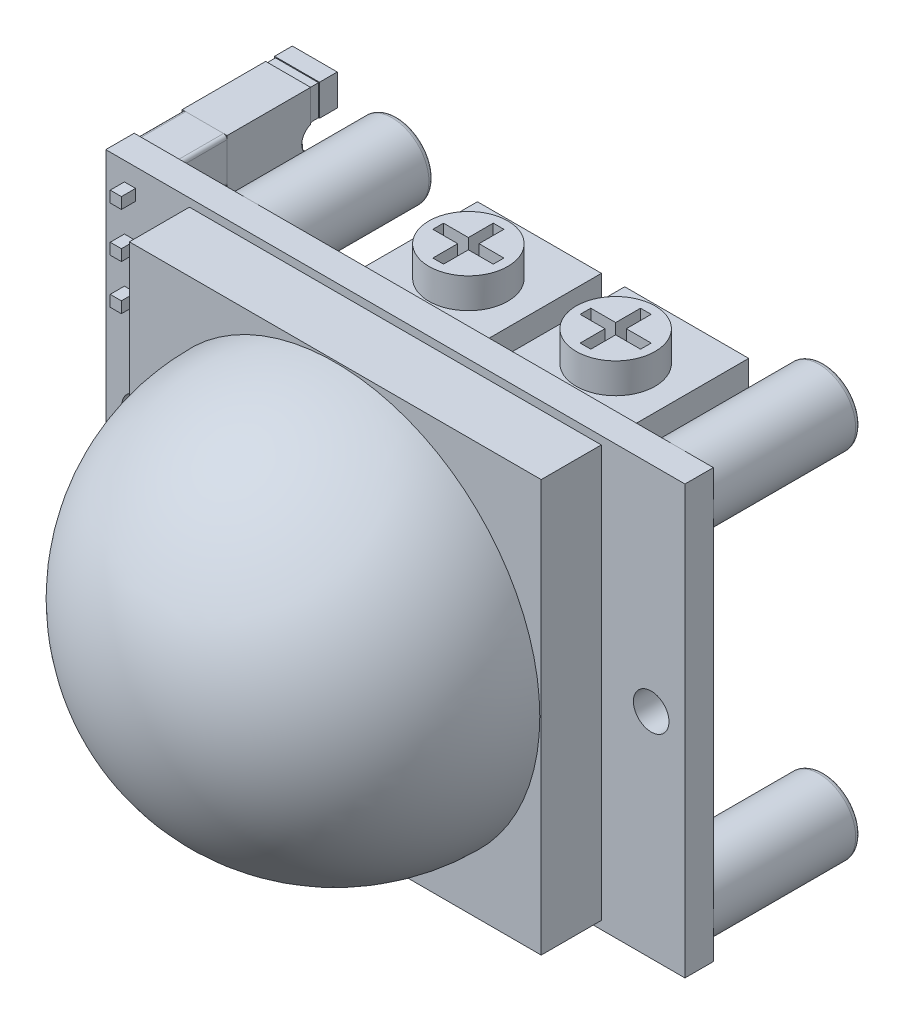
SolidWorks part; units mm, degrees
material "S235 (E24)"
ref_plane "Plan1" through (0, 0, 0) normal (0, 0, 1) x (1, 0, 0)
ref_plane "Plan2" through (0, 0, 0) normal (0, 1, 0) x (1, 0, 0)
ref_plane "Plan3" through (0, 0, 0) normal (1, 0, 0) x (0, 0, -1)
sketch "Esquisse1" plane through (0, 0, 0) normal (0, 0, 1) x (1, 0, 0)
  line L1 (-16.3, 12.04) -> (16.3, 12.04)
  line L2 (-16.3, 12.04) -> (-16.3, -12.04)
  line L3 (-16.3, -12.04) -> (16.3, -12.04)
  line L4 (16.3, 12.04) -> (16.3, -12.04)
  line L5 (-16.3, 12.04) -> (16.3, -12.04) construction
  line L6 (-16.3, -12.04) -> (16.3, 12.04) construction
  point P0 (0, 0)
  dimension "D1" = 24.08
  dimension "D2" = 32.6
extrude "Boss.-Extru.1" add sketch "Esquisse1" along normal blind 1.6
sketch "Esquisse2" plane through (0, 0, 1.6) normal (0, 0, 1) x (1, 0, 0)
  line L1 (-11.59, 11.59) -> (11.59, 11.59)
  line L2 (-11.59, 11.59) -> (-11.59, -11.59)
  line L3 (-11.59, -11.59) -> (11.59, -11.59)
  line L4 (11.59, 11.59) -> (11.59, -11.59)
  line L5 (-11.59, 11.59) -> (11.59, -11.59) construction
  line L6 (-11.59, -11.59) -> (11.59, 11.59) construction
  point P0 (0, 0)
  dimension "D1" = 23.18
extrude "Boss.-Extru.2" add sketch "Esquisse2" along normal blind 3.38
sketch "Esquisse3" plane through (0, 0, 0) normal (0, 1, 0) x (1, 0, 0)
  line L0 (11.59, -4.98) -> (-11.59, -4.98) construction
  line L1 (11.51, -4.98) -> (0, -4.98)
  line L2 (0, -4.98) -> (0, -16.49)
  arc A0 (0, -16.49) -> (11.51, -4.98) centre (0, -4.98) ccw
  dimension "D1" = 23.02
revolve "Révolution1" add sketch "Esquisse3" angle 360 about L2
sketch "Esquisse4" plane through (0, 0, 0) normal (0, 0, -1) x (-1, 0, 0)
  line L0 (16.3, -12.04) -> (-16.3, -12.04) construction
  line L1 (16.3, 12.04) -> (16.3, -12.04) construction
  line L2 (-16.3, -12.04) -> (-16.3, 12.04) construction
  line L3 (-16.3, 12.04) -> (16.3, 12.04) construction
  circle A0 centre (-14.24, -9.98) radius 2.06
  circle A1 centre (-14.24, 9.98) radius 2.06
  circle A2 centre (14.24, -9.98) radius 2.06
  circle A3 centre (9.78, 9.98) radius 2.06
  dimension "D1" = 4.12
  dimension "D2" = 24.02
extrude "Boss.-Extru.3" add sketch "Esquisse4" along normal blind 8.31
fillet "Congé1" radius 0.3 4 edges at (-16.3, -9.98, -8.31) (12.18, -9.98, -8.31) (12.18, 9.98, -8.31) (-11.84, 9.98, -8.31)
sketch "Esquisse5" plane through (0, 0, 0) normal (0, 0, -1) x (-1, 0, 0)
  line L0 (-16.3, -9.98) -> (-16.3, 9.98) construction
  line L1 (-9.92, 9.99) -> (-2.94, 9.99)
  line L2 (-9.92, 9.99) -> (-9.92, 7.21)
  line L3 (-9.92, 7.21) -> (-2.94, 7.21)
  line L4 (-2.94, 9.99) -> (-2.94, 7.21)
  line L5 (-9.92, 9.99) -> (-2.94, 7.21) construction
  line L6 (-9.92, 7.21) -> (-2.94, 9.99) construction
  line L7 (-1.63, 9.99) -> (5.35, 9.99)
  line L8 (-1.63, 9.99) -> (-1.63, 7.21)
  line L9 (-1.63, 7.21) -> (5.35, 7.21)
  line L10 (5.35, 9.99) -> (5.35, 7.21)
  line L11 (-1.63, 9.99) -> (5.35, 7.21) construction
  line L12 (-1.63, 7.21) -> (5.35, 9.99) construction
  line L13 (9.78, 12.04) -> (16.3, 12.04) construction
  point P0 (-6.43, 8.6)
  point P5 (1.86, 8.6)
  dimension "D1" = 6.98
  dimension "D2" = 15.27
  dimension "D3" = 14.67
  dimension "D4" = 2.78
  dimension "D5" = 2.05
extrude "Boss.-Extru.4" add sketch "Esquisse5" along normal blind 8.37
sketch "Esquisse6" plane through (0, 9.99, 0) normal (0, 1, 0) x (1, 0, 0)
  line L0 (-9.78, 0) -> (-16.3, 0) construction
  line L1 (-1.86, 8.37) -> (-1.86, 0) construction
  line L2 (-5.35, 8.37) -> (1.63, 8.37) construction
  line L3 (-5.35, 0) -> (1.63, 0) construction
  line L4 (6.43, 8.37) -> (6.43, 0) construction
  line L5 (2.94, 8.37) -> (9.92, 8.37) construction
  line L6 (2.94, 0) -> (9.92, 0) construction
  line L7 (-1.56, 4.67) -> (-0.16, 4.67)
  line L8 (-3.56, 4.67) -> (-2.16, 4.67)
  line L9 (-3.56, 4.67) -> (-3.56, 4.07)
  line L10 (-3.56, 4.07) -> (-2.16, 4.07)
  line L11 (-0.16, 4.67) -> (-0.16, 4.07)
  line L12 (-3.56, 4.67) -> (-0.16, 4.07) construction
  line L13 (-3.56, 4.07) -> (-0.16, 4.67) construction
  line L14 (4.73, 4.67) -> (6.13, 4.67)
  line L15 (4.73, 4.67) -> (4.73, 4.07)
  line L16 (4.73, 4.07) -> (6.13, 4.07)
  line L17 (8.13, 4.67) -> (8.13, 4.07)
  line L18 (4.73, 4.67) -> (8.13, 4.07) construction
  line L19 (4.73, 4.07) -> (8.13, 4.67) construction
  line L20 (6.13, 2.67) -> (6.73, 2.67)
  line L21 (6.13, 2.67) -> (6.13, 4.07)
  line L22 (6.13, 6.07) -> (6.73, 6.07)
  line L23 (6.73, 2.67) -> (6.73, 4.07)
  line L24 (6.13, 2.67) -> (6.73, 6.07) construction
  line L25 (6.13, 6.07) -> (6.73, 2.67) construction
  line L26 (-2.16, 2.67) -> (-1.56, 2.67)
  line L27 (-2.16, 2.67) -> (-2.16, 4.07)
  line L28 (-2.16, 6.07) -> (-1.56, 6.07)
  line L29 (-1.56, 2.67) -> (-1.56, 4.07)
  line L30 (-2.16, 2.67) -> (-1.56, 6.07) construction
  line L31 (-2.16, 6.07) -> (-1.56, 2.67) construction
  line L32 (-1.56, 4.67) -> (-1.56, 6.07)
  line L33 (-1.56, 4.07) -> (-0.16, 4.07)
  line L34 (-2.16, 4.67) -> (-2.16, 6.07)
  line L35 (6.13, 4.67) -> (6.13, 6.07)
  line L36 (6.73, 4.67) -> (6.73, 6.07)
  line L37 (6.73, 4.07) -> (8.13, 4.07)
  line L38 (6.73, 4.67) -> (8.13, 4.67)
  circle A0 centre (-1.86, 4.37) radius 2.22
  circle A1 centre (6.43, 4.37) radius 2.22
  dimension "D2" = 4.44
  dimension "D1" = 4.37
  dimension "D3" = 0.6
  dimension "D4" = 1.7
extrude "Boss.-Extru.5" add sketch "Esquisse6" along normal blind 1.7
sketch "Esquisse7" plane through (0, 0, 0) normal (0, 0, -1) x (-1, 0, 0)
  line L0 (14.935, 10.675) -> (14.935, 8.135) construction
  line L1 (-1.065, -9.01) -> (1.065, -9.01)
  line L2 (-1.265, -9.21) -> (-1.265, -11.34)
  line L3 (-1.065, -11.54) -> (1.065, -11.54)
  line L4 (1.265, -9.21) -> (1.265, -11.34)
  line L5 (-1.265, -9.01) -> (1.265, -11.54) construction
  line L6 (-1.265, -11.54) -> (1.265, -9.01) construction
  line L7 (-3.605, -9.01) -> (-1.475, -9.01)
  line L8 (-3.805, -9.21) -> (-3.805, -11.34)
  line L9 (-3.605, -11.54) -> (-1.475, -11.54)
  line L10 (-1.275, -9.21) -> (-1.275, -11.34)
  line L11 (-3.805, -9.01) -> (-1.275, -11.54) construction
  line L12 (-3.805, -11.54) -> (-1.275, -9.01) construction
  line L13 (1.475, -9.01) -> (3.605, -9.01)
  line L14 (1.275, -9.21) -> (1.275, -11.34)
  line L15 (1.475, -11.54) -> (3.605, -11.54)
  line L16 (3.805, -9.21) -> (3.805, -11.34)
  line L17 (1.275, -9.01) -> (3.805, -11.54) construction
  line L18 (1.275, -11.54) -> (3.805, -9.01) construction
  line L19 (13.87, 11.94) -> (16, 11.94)
  line L20 (13.67, 11.74) -> (13.67, 9.61)
  line L21 (13.87, 9.41) -> (16, 9.41)
  line L22 (16.2, 11.74) -> (16.2, 9.61)
  line L23 (13.67, 11.94) -> (16.2, 9.41) construction
  line L24 (13.67, 9.41) -> (16.2, 11.94) construction
  line L25 (13.87, 9.4) -> (16, 9.4)
  line L26 (13.67, 9.2) -> (13.67, 7.07)
  line L27 (13.87, 6.87) -> (16, 6.87)
  line L28 (16.2, 9.2) -> (16.2, 7.07)
  line L29 (13.67, 9.4) -> (16.2, 6.87) construction
  line L30 (13.67, 6.87) -> (16.2, 9.4) construction
  line L31 (13.87, 6.86) -> (16, 6.86)
  line L32 (13.67, 6.66) -> (13.67, 4.53)
  line L33 (13.87, 4.33) -> (16, 4.33)
  line L34 (16.2, 6.66) -> (16.2, 4.53)
  line L35 (13.67, 6.86) -> (16.2, 4.33) construction
  line L36 (13.67, 4.33) -> (16.2, 6.86) construction
  line L37 (14.935, 8.135) -> (14.935, 5.595) construction
  line L38 (-2.54, -10.275) -> (0, -10.275) construction
  line L39 (0, -10.275) -> (2.54, -10.275) construction
  line L40 (9.78, 12.04) -> (16.3, 12.04) construction
  line L41 (16.3, 12.04) -> (16.3, -9.98) construction
  line L42 (14.24, -12.04) -> (-14.24, -12.04) construction
  arc A0 (-3.805, -11.34) -> (-3.605, -11.54) centre (-3.605, -11.34) ccw
  arc A1 (-3.605, -9.01) -> (-3.805, -9.21) centre (-3.605, -9.21) ccw
  arc A2 (-1.475, -11.54) -> (-1.275, -11.34) centre (-1.475, -11.34) ccw
  arc A3 (-1.475, -9.01) -> (-1.275, -9.21) centre (-1.475, -9.21) cw
  arc A4 (-1.265, -11.34) -> (-1.065, -11.54) centre (-1.065, -11.34) ccw
  arc A5 (-1.065, -9.01) -> (-1.265, -9.21) centre (-1.065, -9.21) ccw
  arc A6 (1.065, -9.01) -> (1.265, -9.21) centre (1.065, -9.21) cw
  arc A7 (1.475, -9.01) -> (1.275, -9.21) centre (1.475, -9.21) ccw
  arc A8 (1.065, -11.54) -> (1.265, -11.34) centre (1.065, -11.34) ccw
  arc A9 (1.275, -11.34) -> (1.475, -11.54) centre (1.475, -11.34) ccw
  arc A10 (3.605, -11.54) -> (3.805, -11.34) centre (3.605, -11.34) ccw
  arc A11 (3.605, -9.01) -> (3.805, -9.21) centre (3.605, -9.21) cw
  arc A12 (16, 4.33) -> (16.2, 4.53) centre (16, 4.53) ccw
  arc A13 (13.67, 4.53) -> (13.87, 4.33) centre (13.87, 4.53) ccw
  arc A14 (16, 6.86) -> (16.2, 6.66) centre (16, 6.66) cw
  arc A15 (13.87, 6.86) -> (13.67, 6.66) centre (13.87, 6.66) ccw
  arc A16 (13.67, 7.07) -> (13.87, 6.87) centre (13.87, 7.07) ccw
  arc A17 (16, 6.87) -> (16.2, 7.07) centre (16, 7.07) ccw
  arc A18 (16, 9.4) -> (16.2, 9.2) centre (16, 9.2) cw
  arc A19 (13.87, 9.4) -> (13.67, 9.2) centre (13.87, 9.2) ccw
  arc A20 (13.67, 9.61) -> (13.87, 9.41) centre (13.87, 9.61) ccw
  arc A21 (16, 9.41) -> (16.2, 9.61) centre (16, 9.61) ccw
  arc A22 (16, 11.94) -> (16.2, 11.74) centre (16, 11.74) cw
  arc A23 (13.87, 11.94) -> (13.67, 11.74) centre (13.87, 11.74) ccw
  point P0 (0, -10.275)
  point P5 (-2.54, -10.275)
  point P10 (2.54, -10.275)
  point P15 (14.935, 10.675)
  point P20 (14.935, 8.135)
  point P25 (14.935, 5.595)
  point P41 (0, -12.04)
  dimension "D6" = 0.2
  dimension "D1" = 2.54
  dimension "D2" = 0.1
  dimension "D3" = 0.1
  dimension "D4" = 0.5
  dimension "D5" = 2.53
extrude "Boss.-Extru.6" add sketch "Esquisse7" along normal blind 2.6
sketch "Esquisse8" plane through (0, 0, -2.6) normal (0, 0, -1) x (-1, 0, 0)
  line L0 (13.87, 11.74) -> (16, 9.61) construction
  line L1 (16, 9.61) -> (16, 9.2) construction
  line L2 (16, 9.2) -> (13.87, 7.07) construction
  line L3 (13.87, 7.07) -> (13.87, 6.66) construction
  line L4 (13.87, 6.66) -> (16, 4.53) construction
  line L5 (-3.605, -11.34) -> (-1.475, -9.21) construction
  line L6 (-1.475, -9.21) -> (-1.065, -9.21) construction
  line L7 (-1.065, -9.21) -> (1.065, -11.34) construction
  line L8 (1.065, -11.34) -> (1.475, -11.34) construction
  line L9 (1.475, -11.34) -> (3.605, -9.21) construction
  line L11 (-2.855, -9.96) -> (-2.225, -9.96)
  line L12 (-2.855, -9.96) -> (-2.855, -10.59)
  line L13 (-2.855, -10.59) -> (-2.225, -10.59)
  line L14 (-2.225, -9.96) -> (-2.225, -10.59)
  line L15 (-2.855, -9.96) -> (-2.225, -10.59) construction
  line L16 (-2.855, -10.59) -> (-2.225, -9.96) construction
  line L17 (-0.315, -9.96) -> (0.315, -9.96)
  line L18 (-0.315, -9.96) -> (-0.315, -10.59)
  line L19 (-0.315, -10.59) -> (0.315, -10.59)
  line L20 (0.315, -9.96) -> (0.315, -10.59)
  line L21 (-0.315, -9.96) -> (0.315, -10.59) construction
  line L22 (-0.315, -10.59) -> (0.315, -9.96) construction
  line L23 (2.855, -9.96) -> (2.225, -9.96)
  line L24 (2.855, -9.96) -> (2.855, -10.59)
  line L25 (2.855, -10.59) -> (2.225, -10.59)
  line L26 (2.225, -9.96) -> (2.225, -10.59)
  line L27 (2.855, -9.96) -> (2.225, -10.59) construction
  line L28 (2.855, -10.59) -> (2.225, -9.96) construction
  line L29 (14.62, 10.99) -> (15.25, 10.99)
  line L30 (14.62, 10.99) -> (14.62, 10.36)
  line L31 (14.62, 10.36) -> (15.25, 10.36)
  line L32 (15.25, 10.99) -> (15.25, 10.36)
  line L33 (14.62, 10.99) -> (15.25, 10.36) construction
  line L34 (14.62, 10.36) -> (15.25, 10.99) construction
  line L35 (14.62, 7.82) -> (15.25, 7.82)
  line L36 (14.62, 7.82) -> (14.62, 8.45)
  line L37 (14.62, 8.45) -> (15.25, 8.45)
  line L38 (15.25, 7.82) -> (15.25, 8.45)
  line L39 (14.62, 7.82) -> (15.25, 8.45) construction
  line L40 (14.62, 8.45) -> (15.25, 7.82) construction
  line L41 (15.25, 5.28) -> (14.62, 5.28)
  line L42 (15.25, 5.28) -> (15.25, 5.91)
  line L43 (15.25, 5.91) -> (14.62, 5.91)
  line L44 (14.62, 5.28) -> (14.62, 5.91)
  line L45 (15.25, 5.28) -> (14.62, 5.91) construction
  line L46 (15.25, 5.91) -> (14.62, 5.28) construction
  point P22 (-2.54, -10.275)
  point P29 (0, -10.275)
  point P34 (2.54, -10.275)
  point P39 (14.935, 10.675)
  point P44 (14.935, 8.135)
  point P49 (14.935, 5.595)
  dimension "D1" = 0.63
extrude "Boss.-Extru.7" add sketch "Esquisse8" along normal blind 5.79 and the other way blind 5
sketch "Esquisse9" plane through (0, 0, -2.6) normal (0, 0, -1) x (-1, 0, 0)
  line L0 (13.67, 11.74) -> (13.67, 9.61) construction
  line L1 (13.67, 11.94) -> (16.2, 11.94)
  line L2 (13.67, 11.94) -> (13.67, 6.87)
  line L3 (13.67, 6.87) -> (16.2, 6.87)
  line L4 (16.2, 11.94) -> (16.2, 6.87)
  line L5 (16.2, 9.61) -> (16.2, 11.74) construction
  line L6 (13.87, 6.87) -> (16, 6.87) construction
  line L7 (16, 11.94) -> (13.87, 11.94) construction
extrude "Boss.-Extru.8" add sketch "Esquisse9" along normal blind 6.2 separate body
sketch "Esquisse10" plane through (0, 0, -8.8) normal (0, 0, -1) x (-1, 0, 0)
  line L0 (16.2, 11.94) -> (13.67, 6.87) construction
  line L1 (16.2, 6.87) -> (16.2, 11.94) construction
  line L2 (13.87, 11.74) -> (16, 11.74)
  line L3 (13.87, 11.74) -> (13.87, 7.07)
  line L4 (13.87, 7.07) -> (16, 7.07)
  line L5 (16, 11.74) -> (16, 7.07)
  line L6 (13.87, 11.74) -> (16, 7.07) construction
  line L7 (13.87, 7.07) -> (16, 11.74) construction
  line L8 (16.2, 11.94) -> (13.67, 11.94) construction
  line L9 (14.62, 7.82) -> (15.25, 7.82) construction
  line L10 (14.62, 10.99) -> (15.25, 10.99)
  line L11 (14.62, 10.99) -> (14.62, 10.36)
  line L12 (14.62, 10.36) -> (15.25, 10.36)
  line L13 (15.25, 10.99) -> (15.25, 10.36)
  line L14 (14.62, 8.45) -> (15.25, 8.45)
  line L15 (14.62, 8.45) -> (14.62, 7.82)
  line L16 (14.62, 7.82) -> (15.25, 7.82)
  line L17 (15.25, 8.45) -> (15.25, 7.82)
  point P4 (14.935, 9.405)
  dimension "D1" = 0.2
  dimension "D2" = 0.2
extrude "Enlèv. mat.-Extru.1" cut sketch "Esquisse10" against normal blind 1.5
sketch "Esquisse11" plane through (0, 0, -8.8) normal (0, 0, -1) x (-1, 0, 0)
  line L1 (14.62, 10.99) -> (15.25, 10.99)
  line L2 (14.62, 10.99) -> (14.62, 10.36)
  line L3 (14.62, 10.36) -> (15.25, 10.36)
  line L4 (15.25, 10.99) -> (15.25, 10.36)
  line L5 (14.62, 8.45) -> (15.25, 8.45)
  line L6 (14.62, 8.45) -> (14.62, 7.82)
  line L7 (14.62, 7.82) -> (15.25, 7.82)
  line L8 (15.25, 8.45) -> (15.25, 7.82)
extrude "Enlèv. mat.-Extru.2" cut sketch "Esquisse11" against normal blind 1
sketch "Esquisse12" plane through (0, 0, -7.3) normal (0, 0, -1) x (-1, 0, 0)
  line L0 (16.2, 11.94) -> (13.67, 6.87) construction
  line L1 (13.67, 11.94) -> (16.2, 11.94)
  line L2 (13.67, 11.94) -> (13.67, 6.87)
  line L3 (13.67, 6.87) -> (16.2, 6.87)
  line L4 (16.2, 11.94) -> (16.2, 6.87)
  line L6 (13.7248, 6.92) -> (16.1452, 6.92)
  line L7 (13.7248, 6.92) -> (13.7248, 11.89)
  line L8 (13.7248, 11.89) -> (16.1452, 11.89)
  line L9 (16.1452, 6.92) -> (16.1452, 11.89)
  line L10 (13.7248, 6.92) -> (16.1452, 11.89) construction
  line L11 (13.7248, 11.89) -> (16.1452, 6.92) construction
  point P6 (14.935, 9.405)
  dimension "D1" = 0.0548
  dimension "D2" = 0.05
extrude "Enlèv. mat.-Extru.3" cut sketch "Esquisse12" along normal blind 0.5
sketch "Esquisse13" plane through (0, 0, -8.8) normal (0, 0, -1) x (-1, 0, 0)
  line L0 (13.67, 9.405) -> (13.87, 9.405) construction
  line L1 (13.67, 11.94) -> (13.67, 6.87) construction
  line L2 (13.87, 11.74) -> (13.87, 7.07) construction
  line L3 (13.87, 9.405) -> (16, 9.405) construction
  line L4 (16, 7.07) -> (16, 11.74) construction
  line L5 (16, 9.405) -> (16.2, 9.405) construction
  line L6 (16.2, 6.87) -> (16.2, 11.94) construction
  line L7 (16.2, 7.07) -> (16.2, 9.2) construction
  line L8 (16, 10.18) -> (16.2, 10.18)
  line L9 (16, 10.18) -> (13.87, 10.18)
  line L10 (16, 8.63) -> (16.2, 8.63)
  line L11 (16.2, 10.18) -> (16.2, 8.63)
  line L12 (16, 10.18) -> (16.2, 8.63) construction
  line L13 (16, 8.63) -> (16.2, 10.18) construction
  line L14 (13.87, 8.63) -> (16, 8.63)
  line L15 (13.67, 10.18) -> (13.87, 10.18)
  line L16 (13.67, 10.18) -> (13.67, 8.63)
  line L17 (13.67, 8.63) -> (13.87, 8.63)
  line L19 (13.67, 10.18) -> (13.87, 8.63) construction
  line L20 (13.67, 8.63) -> (13.87, 10.18) construction
  point P6 (16.1, 9.405)
  point P19 (13.77, 9.405)
  dimension "D1" = 1.55
extrude "Enlèv. mat.-Extru.4" cut sketch "Esquisse13" against normal blind 2
fillet "Congé4" radius 0.77 2 edges at (-14.935, 10.18, -6.8) (-14.935, 8.63, -6.8)
sketch "Esquisse15" plane through (0, 0, 1.6) normal (0, 0, 1) x (1, 0, 0)
  line L0 (-16.3, 0) -> (-14.4, 0) construction
  line L1 (-16.3, 12.04) -> (-16.3, -12.04) construction
  line L2 (-14.4, 0) -> (14.4, 0) construction
  line L3 (14.4, 0) -> (16.3, 0) construction
  line L4 (16.3, -12.04) -> (16.3, 12.04) construction
  circle A0 centre (14.4, 0) radius 1
  circle A1 centre (-14.4, 0) radius 1
  dimension "D1" = 2
  dimension "D2" = 28.8
extrude "Enlèv. mat.-Extru.5" cut sketch "Esquisse15" against normal up to surface (1.6 mm away) up to face at (-14.935, 8.135, 0)
sketch "Esquisse17" plane through (0, 0, 0) normal (0, 0, -1) x (-1, 0, 0)
  line L0 (-1.9981, -8.2905) -> (-1.9981, -4.0923) construction
  text T0 "+5V\r\nData\r\nGND" font "Arial" height in points 4
extrude "Boss.-Extru.10" add sketch "Esquisse17" along normal blind 0.01
sketch "Esquisse18" plane through (0, 0, 0) normal (0, 0, -1) x (-1, 0, 0)
  line L0 (-0.12, -2.5475) -> (-0.12, 6.1739) construction
  text T0 "Sensitivity\r\nCW to HIGH\r\nACW to LOW" font "Arial" height in points 4
extrude "Boss.-Extru.11" add sketch "Esquisse18" along normal blind 0.01
sketch "Esquisse19" plane through (0, 0, 0) normal (0, 0, -1) x (-1, 0, 0)
  line L0 (-8.5661, -2.0365) -> (-8.5661, 5.9009) construction
  text T0 "Tile Delay\r\nCW +\r\nACW -" font "Arial" height in points 4
extrude "Boss.-Extru.12" add sketch "Esquisse19" along normal blind 0.01
sketch "Esquisse20" plane through (0, 0, 0) normal (0, 0, -1) x (-1, 0, 0)
  line L0 (13.1589, 6.1361) -> (13.1589, 11.2219) construction
  text T0 "H     L" font "Arial" height in points 4
extrude "Boss.-Extru.13" add sketch "Esquisse20" along normal blind 0.01
sketch "Esquisse21" plane through (0, 0, 0) normal (0, 0, -1) x (-1, 0, 0)
  line L0 (9.6606, -7.2693) -> (9.6606, 7.5766) construction
  text T0 "H : Reapeat Trigger\r\nL : Single Trigger" font "Arial" height in points 4
extrude "Boss.-Extru.14" add sketch "Esquisse21" along normal blind 0.01
